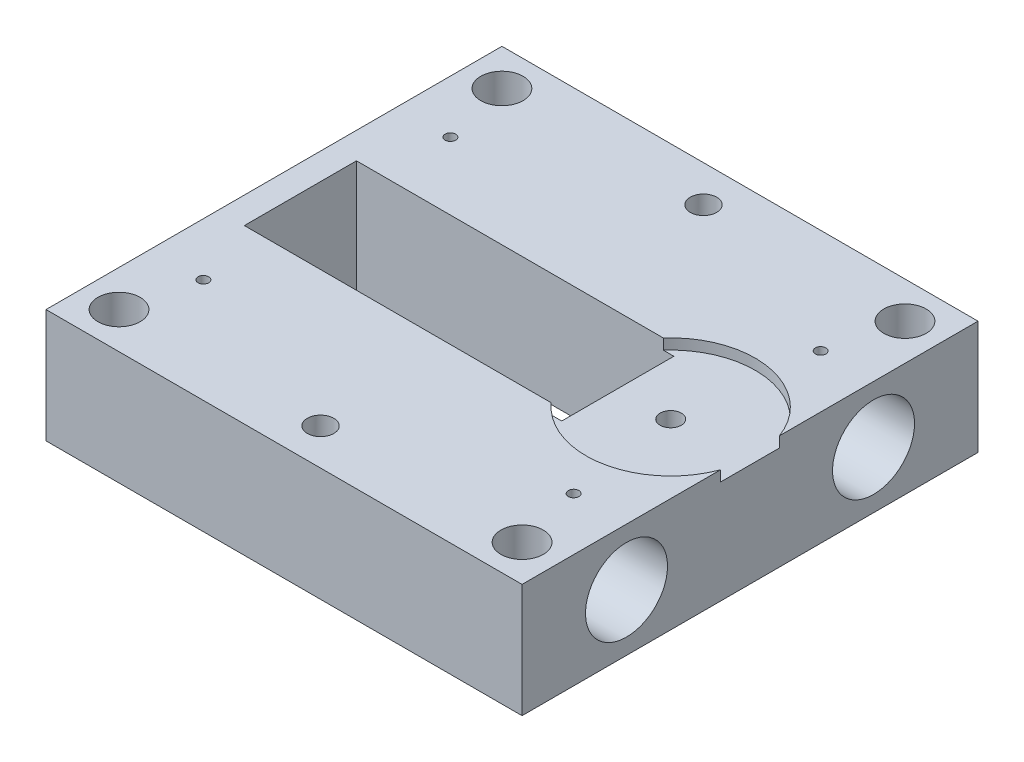
SolidWorks part; units mm, degrees
ref_plane "Front Plane" through (0, 0, 0) normal (0, 0, 1) x (1, 0, 0)
ref_plane "Top Plane" through (0, 0, 0) normal (0, 1, 0) x (1, 0, 0)
ref_plane "Right Plane" through (0, 0, 0) normal (1, 0, 0) x (0, 0, -1)
sketch "Sketch2" plane through (0, 0, 0) normal (1, 0, 0) x (0, 0, -1)
  line L0 (-23.35, 0) -> (23.35, 0) construction
  line L5 (-38.1, 0) -> (38.1, 0) construction
  line L6 (-43.1, -10.75) -> (43.1, -10.75)
  line L7 (-43.1, -10.75) -> (-43.1, 10.75)
  line L8 (-43.1, 10.75) -> (43.1, 10.75)
  line L9 (43.1, -10.75) -> (43.1, 10.75)
  line L10 (-43.1, -10.75) -> (43.1, 10.75) construction
  line L11 (-43.1, 10.75) -> (43.1, -10.75) construction
  circle A0 centre (-23.35, 0) radius 7.75
  circle A1 centre (23.35, 0) radius 7.75
  point P4 (0, 0)
  point P6 (0, 0)
  point P12 (-23.35, 7.75)
  point P14 (-31.1, 0)
  dimension "D1" = 15.5
  dimension "D2" = 3
  dimension "D3" = 76.2
  dimension "D4" = 5
  dimension "D5" = 7
extrude "Boss-Extrude1" add sketch "Sketch2" along normal mid plane 90
sketch "Sketch3" plane through (0, -10.75, 0) normal (0, -1, 0) x (1, 0, 0)
  line L1 (-38.1, -36.195) -> (38.1, -36.195) construction
  line L2 (-38.1, -36.195) -> (-38.1, 36.195) construction
  line L3 (-38.1, 36.195) -> (38.1, 36.195) construction
  line L4 (38.1, -36.195) -> (38.1, 36.195) construction
  line L5 (-38.1, -36.195) -> (38.1, 36.195) construction
  line L6 (-38.1, 36.195) -> (38.1, -36.195) construction
  circle A0 centre (-38.1, 36.195) radius 1.375
  circle A1 centre (38.1, 36.195) radius 1.375
  circle A2 centre (38.1, -36.195) radius 1.375
  circle A3 centre (-38.1, -36.195) radius 1.375
  point P0 (0, 0)
  dimension "D3" = 2.75
  dimension "D1" = 72.39
  dimension "D2" = 76.2
extrude "Cut-Extrude1" cut sketch "Sketch3" against normal through all
sketch "Sketch4" plane through (0, 10.75, 0) normal (0, 1, 0) x (1, 0, 0)
  circle A0 centre (-38.1, -36.195) radius 4
  circle A1 centre (-38.1, 36.195) radius 4
  circle A2 centre (38.1, 36.195) radius 4
  circle A3 centre (38.1, -36.195) radius 4
  dimension "D1" = 8
extrude "Cut-Extrude2" cut sketch "Sketch4" against normal offset from surface (18.5 mm away) 3 up to face at (-38.1, -10.75, -37.57)
sketch "Sketch5" plane through (0, 0, 0) normal (1, 0, 0) x (0, 0, -1)
  circle A0 centre (23.35, 0) radius 7.75 construction
  circle A1 centre (-23.35, 0) radius 7.75 construction
  circle A2 centre (23.35, 0) radius 7.75
  circle A3 centre (-23.35, 0) radius 7.75
  circle A4 centre (-23.35, 0) radius 5
  circle A5 centre (23.35, 0) radius 5
  dimension "D1" = 10
extrude "Boss-Extrude2" add sketch "Sketch5" along normal mid plane 42
sketch "Sketch6" plane through (0, 10.75, 0) normal (0, 1, 0) x (1, 0, 0)
  line L0 (45, 43.1) -> (45, -43.1) construction
  circle A0 centre (30, 0) radius 2
  circle A1 centre (0, -36.195) radius 2.5
  circle A2 centre (0, 36.195) radius 2.5
  circle A3 centre (-38.1, -36.195) radius 1.375 construction
  circle A4 centre (-38.1, -36.195) radius 1.375 construction
  circle A5 centre (-38.1, 36.195) radius 1.375 construction
  circle A6 centre (-38.1, 36.195) radius 1.375 construction
  dimension "D1" = 4
  dimension "D3" = 5
  dimension "D2" = 15
extrude "Cut-Extrude3" cut sketch "Sketch6" against normal through all
sketch "Sketch7" plane through (0, -10.75, 0) normal (0, -1, 0) x (1, 0, 0)
  circle A0 centre (30, 0) radius 5
  circle A1 centre (0, 36.195) radius 5
  circle A2 centre (0, -36.195) radius 5
  dimension "D1" = 10
extrude "Cut-Extrude4" cut sketch "Sketch7" against normal offset from surface (17.5 mm away) 4 up to face at (30, 10.75, 2)
sketch "Sketch8" plane through (0, 10.75, 0) normal (0, 1, 0) x (1, 0, 0)
  line L0 (45, -31.1) -> (45, -15.6) construction
  line L1 (35, 23.35) -> (-35, 23.35) construction
  line L2 (35, 23.35) -> (35, -23.35) construction
  line L3 (35, -23.35) -> (-35, -23.35) construction
  line L4 (-35, 23.35) -> (-35, -23.35) construction
  line L5 (35, 23.35) -> (-35, -23.35) construction
  line L6 (35, -23.35) -> (-35, 23.35) construction
  line L7 (45, -31.1) -> (45, -15.6) construction
  line L8 (45, 43.1) -> (45, -43.1) construction
  circle A0 centre (35, -23.35) radius 1
  circle A1 centre (-35, -23.35) radius 1
  circle A2 centre (-35, 23.35) radius 1
  circle A3 centre (35, 23.35) radius 1
  point P0 (0, 0)
  point P8 (45, -23.35)
  dimension "D2" = 2
  dimension "D1" = 10
extrude "Cut-Extrude5" cut sketch "Sketch8" against normal up to next
sketch "Sketch9" plane through (0, 10.75, 0) normal (0, 1, 0) x (1, 0, 0)
  line L0 (-21, -15.6) -> (-45, -15.6) construction
  line L1 (20, -10.6) -> (-40, -10.6)
  line L2 (20, -10.6) -> (20, 10.6)
  line L3 (20, 10.6) -> (-40, 10.6)
  line L4 (-40, -10.6) -> (-40, 10.6)
  line L5 (20, -10.6) -> (-40, 10.6) construction
  line L6 (20, 10.6) -> (-40, -10.6) construction
  line L7 (-45, 43.1) -> (-45, -43.1) construction
  circle A0 centre (30, 0) radius 5 construction
  circle A1 centre (30, 0) radius 2 construction
  circle A2 centre (30, 0) radius 2 construction
  point P0 (-10, 0)
  point P12 (25, 0)
  dimension "D1" = 5
  dimension "D2" = 5
  dimension "D3" = 5
extrude "Cut-Extrude6" cut sketch "Sketch9" against normal through all
sketch "Sketch10" plane through (0, 10.75, 0) normal (0, 1, 0) x (1, 0, 0)
  circle A0 centre (30, 0) radius 16
  dimension "D1" = 32
extrude "Cut-Extrude7" cut sketch "Sketch10" against normal blind 2
sketch "Sketch11" plane through (0, 6.75, 0) normal (0, -1, 0) x (1, 0, 0)
  circle A0 centre (30, 0) radius 2 construction
  circle A1 centre (30, 0) radius 5
  circle A2 centre (30, 0) radius 5
  circle A3 centre (30, 0) radius 2
  dimension "D1" = 0
extrude "Boss-Extrude3" add sketch "Sketch11" along normal offset from surface (2 mm away) 4 up to face at (28.1469, 8.75, 0)
